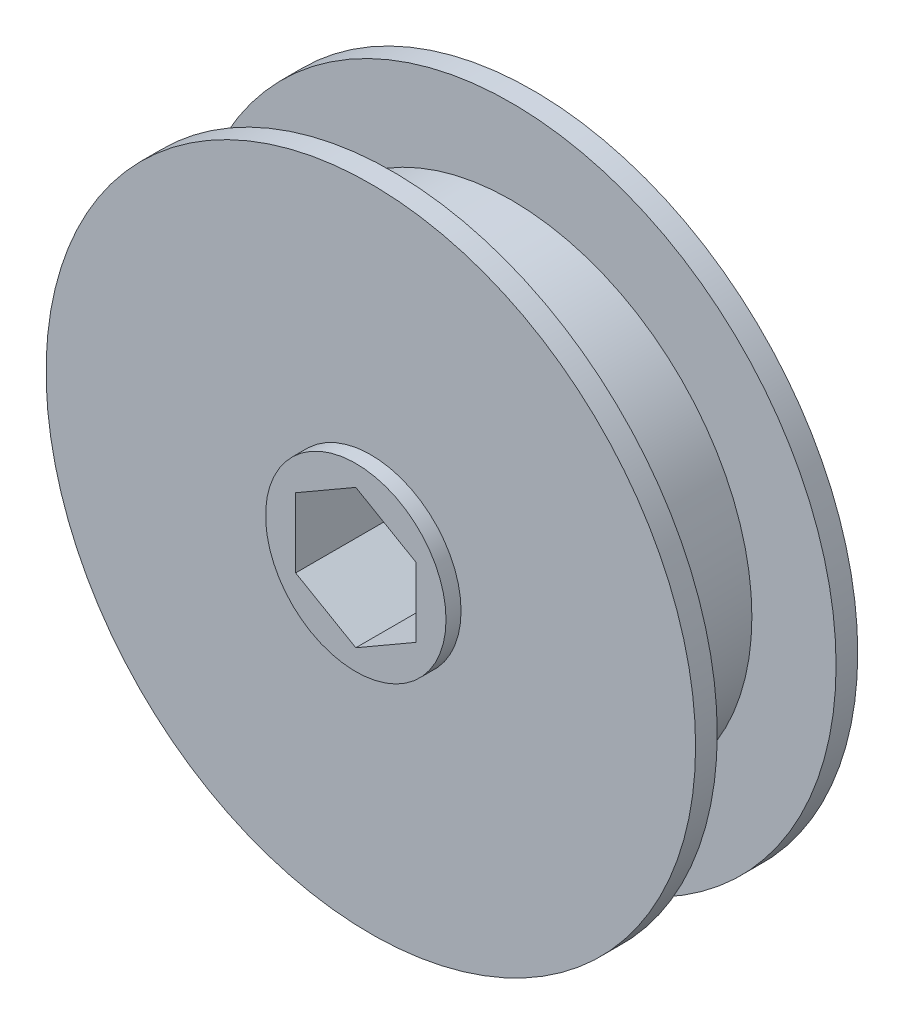
SolidWorks part; units mm, degrees
material "Nylon 101"
ref_plane "Front Plane" through (0, 0, 0) normal (0, 0, 1) x (1, 0, 0)
ref_plane "Top Plane" through (0, 0, 0) normal (0, 1, 0) x (1, 0, 0)
ref_plane "Right Plane" through (0, 0, 0) normal (1, 0, 0) x (0, 0, -1)
sketch "Sketch2" plane through (0, 0, 0) normal (0, 0, 1) x (1, 0, 0)
  line L1 (0, 7.3323) -> (-6.35, 3.6662)
  line L2 (-6.35, 3.6662) -> (-6.35, -3.6662)
  line L3 (-6.35, -3.6662) -> (0, -7.3323)
  line L4 (0, -7.3323) -> (6.35, -3.6662)
  line L5 (6.35, -3.6662) -> (6.35, 3.6662)
  line L6 (6.35, 3.6662) -> (0, 7.3323)
  circle A0 centre (0, 0) radius 25.4
  circle A1 centre (0, 0) radius 6.35 construction
  dimension "D1" = 50.8
  dimension "D2" = 12.7
extrude "Boss-Extrude3" add sketch "Sketch2" along normal mid plane 16.4211
sketch "Sketch3" plane through (0, 0, 8.2105) normal (0, 0, 1) x (1, 0, 0)
  line L1 (0, 7.3323) -> (-6.35, 3.6662)
  line L2 (-6.35, 3.6662) -> (-6.35, -3.6662)
  line L3 (-6.35, -3.6662) -> (0, -7.3323)
  line L4 (0, -7.3323) -> (6.35, -3.6662)
  line L5 (6.35, -3.6662) -> (6.35, 3.6662)
  line L6 (6.35, 3.6662) -> (0, 7.3323)
  circle A0 centre (0, 0) radius 34.29
  circle A1 centre (0, 0) radius 6.35 construction
  dimension "D1" = 12.7
  dimension "D2" = 68.58
extrude "Boss-Extrude4" add sketch "Sketch3" along normal mid plane 3.8735
sketch "Sketch4" plane through (0, 0, 10.1473) normal (0, 0, 1) x (1, 0, 0)
  circle A0 centre (0, 0) radius 9.525
  circle A1 centre (0, 0) radius 34.29
  circle A2 centre (0, 0) radius 34.29 construction
  dimension "D1" = 19.05
extrude "Cut-Extrude1" cut sketch "Sketch4" against normal blind 1.5875
mirror "Mirror1" about plane through (0, 0, 0) normal (0, 0, 1) of "Cut-Extrude1", "Boss-Extrude4"
